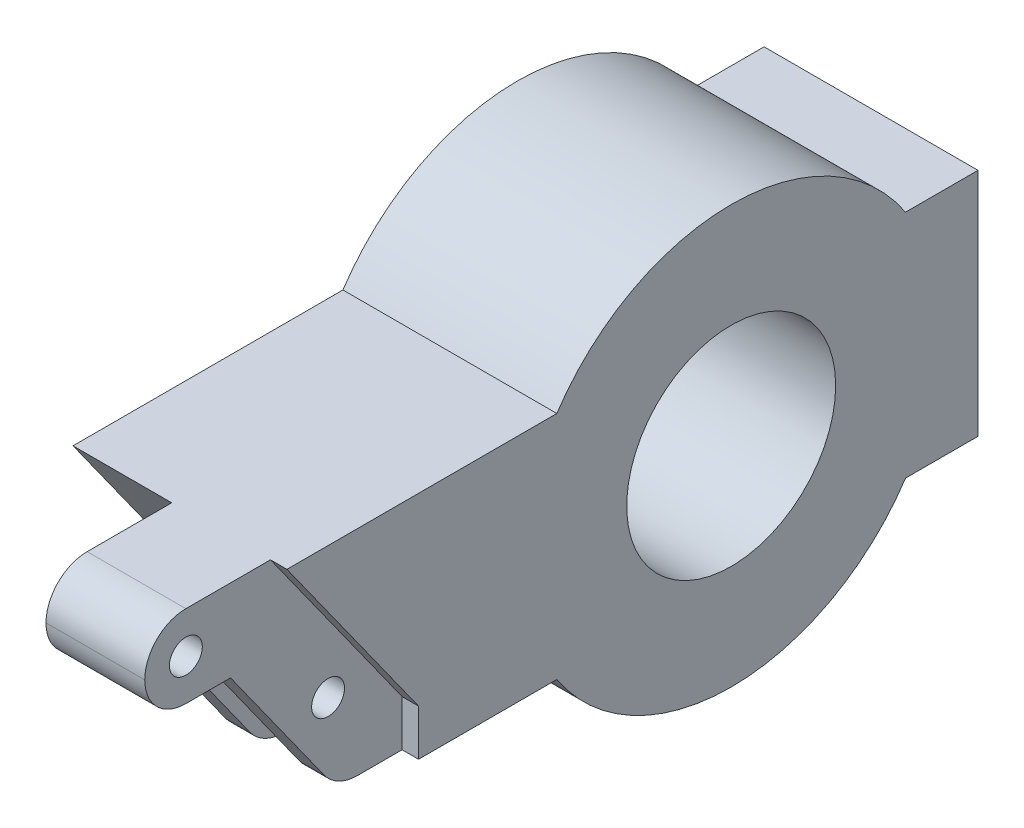
SolidWorks part; units mm, degrees
material "Plain Carbon Steel"
ref_plane "Front Plane" through (0, 0, 0) normal (0, 0, 1) x (1, 0, 0)
ref_plane "Top Plane" through (0, 0, 0) normal (0, 1, 0) x (1, 0, 0)
ref_plane "Right Plane" through (0, 0, 0) normal (1, 0, 0) x (0, 0, -1)
sketch "Sketch1" plane through (0, 0, 0) normal (1, 0, 0) x (0, 0, -1)
  line L0 (-45.1764, 3.0469) -> (-38.7478, -5.9531)
  line L1 (-36.7135, -7) -> (-25.5967, -7)
  line L3 (-43.142, 7) -> (-25.5967, 7)
  line L4 (0, -7) -> (0, 7)
  line L5 (-4.4033, 7) -> (0, 7)
  line L6 (-18, 20) -> (0, 20) construction
  line L7 (0, 20) -> (0, 7) construction
  line L8 (-18, 20) -> (-28.9083, 7) construction
  line L9 (-4.4033, -7) -> (0, -7)
  arc A2 (-38.7478, -5.9531) -> (-36.7135, -7) centre (-36.7135, -4.5) ccw
  arc A3 (-45.1764, 3.0469) -> (-43.142, 7) centre (-43.142, 4.5) cw
  circle A5 centre (-38.4992, -2) radius 1
  circle A6 centre (-15, 0) radius 6.35
  arc A7 (-25.5967, -7) -> (-4.4033, -7) centre (-15, 0) ccw
  arc A8 (-4.4033, 7) -> (-25.5967, 7) centre (-15, 0) ccw
  point P0 (0, 0)
  point P2 (0, 0)
  point P11 (0, 7)
  point P14 (-38, -7)
  point P17 (-48, 7)
  dimension "D4" = 2.5
  dimension "D5" = 2
  dimension "D9" = 5
  dimension "D11" = 12.7
  dimension "D1" = 14
  dimension "D2" = 48
  dimension "D3" = 10
  dimension "D6" = 27
  dimension "D7" = 18
  dimension "D8" = 50
  dimension "D10" = 2.5
  dimension "D12" = 15
  dimension "0.25 in" = 6.35
extrude "Boss-Extrude1" add sketch "Sketch1" along normal mid plane 18 contours L7 L6 L3 | A3 L0 A2 L1 L4 L3 region at (0, 5.4049, 44.9005)
sketch "Sketch2" plane through (0, 7, 0) normal (0, 1, 0) x (1, 0, 0)
  line L0 (9, -43.142) -> (-9, -43.142) construction
  line L1 (3, -49.642) -> (-3, -49.642)
  line L2 (3, -49.642) -> (3, -43.142)
  line L3 (3, -43.142) -> (-3, -43.142)
  line L4 (-3, -49.642) -> (-3, -43.142)
  line L5 (3, -49.642) -> (-3, -43.142) construction
  line L6 (3, -43.142) -> (-3, -49.642) construction
  point P0 (0, -46.392)
  dimension "D1" = 6.5
  dimension "D2" = 6
extrude "Boss-Extrude2" add sketch "Sketch2" against normal blind 5
sketch "Sketch3" plane through (3, 0, 0) normal (1, 0, 0) x (0, 0, -1)
  line L0 (-49.642, 2) -> (-49.642, 7) construction
  line L1 (-49.642, 2) -> (-44.4286, 2) construction
  circle A0 centre (-47.142, 4.5) radius 1
  dimension "D1" = 2
  dimension "D2" = 2.5
  dimension "D3" = 2.5
extrude "Cut-Extrude1" cut sketch "Sketch3" against normal up to next
fillet "Fillet1" radius 2.5 2 edges at (0, 2, 49.642) (0, 7, 49.642)
sketch "Sketch4" plane through (0, -7, 0) normal (0, -1, 0) x (1, 0, 0)
  line L0 (-9, 45.1764) -> (-9, 38.7478) construction
  line L1 (1.5, 35.9978) -> (-1.5, 35.9978)
  line L2 (1.5, 35.9978) -> (1.5, 43.9978)
  line L3 (1.5, 43.9978) -> (-1.5, 43.9978)
  line L4 (-1.5, 35.9978) -> (-1.5, 43.9978)
  line L5 (1.5, 35.9978) -> (-1.5, 43.9978) construction
  line L6 (1.5, 43.9978) -> (-1.5, 35.9978) construction
  line L8 (9, 38.7478) -> (-9, 38.7478) construction
  point P0 (0, 39.9978)
  point P7 (0, 43.9978)
  dimension "D1" = 8
  dimension "D2" = 3
  dimension "D3" = 1.25
  dimension "D4" = 9
extrude "Cut-Extrude3" cut sketch "Sketch4" against normal blind 7.5
sketch "Sketch6" plane through (9, 0, 0) normal (1, 0, 0) x (0, 0, -1)
  line L0 (-48, 7) -> (-38, -7)
  line L9 (-42, 7) -> (-34, -4.2)
  line L11 (-48, 7) -> (-42, 7)
  line L14 (-45.1764, 3.0469) -> (-38.7478, -5.9531) construction
  line L19 (-34, -4.2) -> (-34, -7)
  line L21 (-38, -7) -> (-34, -7)
  line L22 (-36.7135, -7) -> (-25.5967, -7) construction
  line L23 (-47.142, 7) -> (-43.142, 7) construction
  point P11 (-33.7094, -7.4068)
  point P14 (0, 0)
  point P15 (0, 0)
  dimension "D1" = 6
  dimension "D2" = 4
extrude "Cut-Extrude8" cut sketch "Sketch6" against normal up to surface (6 mm away) up to face at (3, 4.5, 46.142)
sketch "Sketch8" plane through (-9, 0, 0) normal (-1, 0, 0) x (0, 0, 1)
  line L2 (38, -7) -> (48, 7)
  line L4 (48, 7) -> (42, 7)
  line L6 (42, 7) -> (34, -4.2)
  line L7 (34, -4.2) -> (34, -7)
  line L9 (34, -7) -> (38, -7)
  line L11 (43.142, 7) -> (47.142, 7) construction
  point P0 (42.0812, 6.0162)
  dimension "D1" = 6
  dimension "D2" = 4
extrude "Cut-Extrude9" cut sketch "Sketch8" against normal up to surface (6 mm away) up to face at (-3, 4.5, 48.142)
sketch "Sketch9" plane through (9, 0, 0) normal (1, 0, 0) x (0, 0, -1)
  line L0 (0, -7) -> (0, 7) construction
  line L1 (-49.642, 12.7) -> (0, 12.7)
  line L2 (-49.642, 12.7) -> (-49.642, -12.7)
  line L3 (-49.642, -12.7) -> (0, -12.7)
  line L4 (0, 12.7) -> (0, -12.7)
  line L5 (-49.642, 12.7) -> (0, -12.7) construction
  line L6 (-49.642, -12.7) -> (0, 12.7) construction
  arc A1 (-25.5967, -7) -> (-4.4033, -7) centre (-15, 0) ccw construction
  arc A2 (-4.4033, 7) -> (-25.5967, 7) centre (-15, 0) ccw construction
  point P12 (-51.1655, 12.8729)
  point P17 (0, 0)
extrude "Cut-Extrude11" cut sketch "Sketch9" against normal blind 5 contours L3 L4 L1 L2
